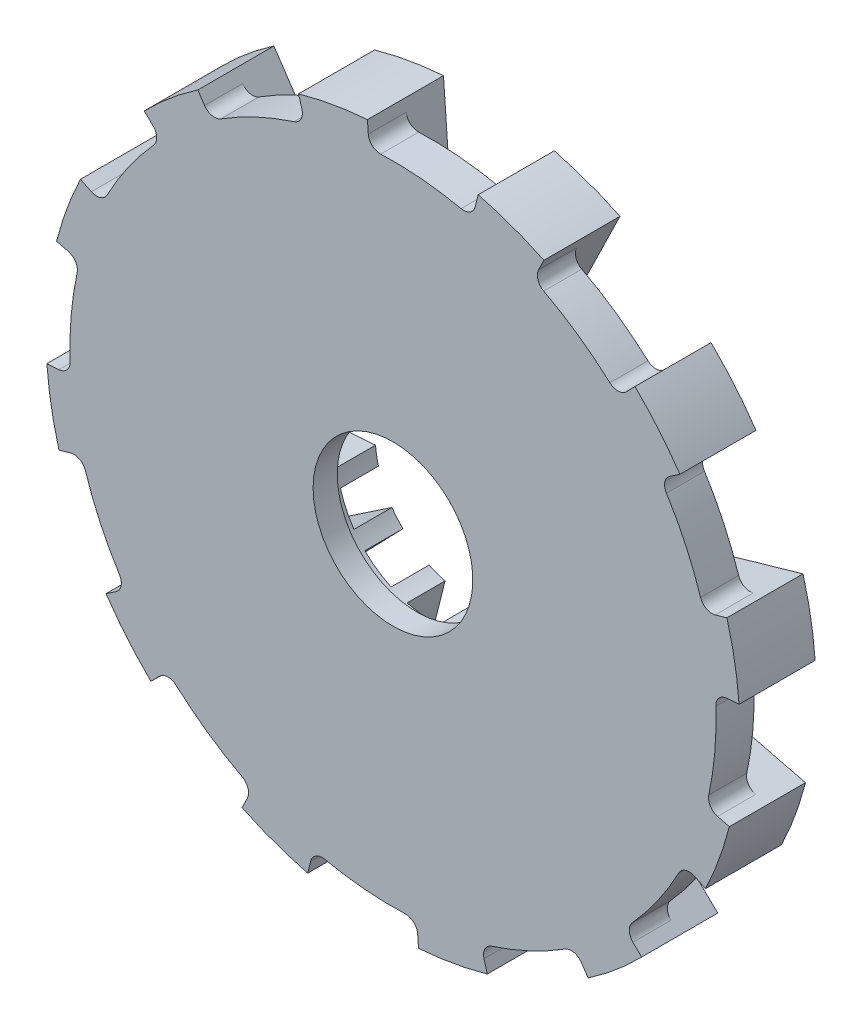
SolidWorks part; units mm, degrees
material "6061-T6 (SS)"
ref_plane "Front Plane" through (0, 0, 0) normal (1, 0, 0) x (0, 1, 0)
ref_plane "Top Plane" through (0, 0, 0) normal (0, 0, 1) x (0, 1, 0)
ref_plane "Right Plane" through (0, 0, 0) normal (0, 1, 0) x (-1, 0, 0)
ref_axis "Axis1" through (0, 0, 20.005) along (0, 0, -1)
sketch "Sketch1" plane through (0, 0, 0) normal (0, 0, 1) x (0, 1, 0)
  line L0 (0, 0) -> (0, 101.4736) construction
  line L1 (0, 0) -> (-35.1798, 75.4434) construction
  line L2 (-48.8686, 71.8573) -> (-10.3133, 14.6967)
  line L3 (-4.6291, 17.3473) -> (-23.6338, 83.6245)
  line L4 (-44.6805, 71.0131) -> (-25.6791, 79.8736) construction
  circle A0 centre (0, 0) radius 86.9
  arc A2 (-10.3133, 14.6967) -> (-4.6291, 17.3473) centre (-7.6811, 16.4721) ccw
  arc A3 (-46.2782, 73.5523) -> (-26.5973, 82.7296) centre (0, 0) cw
  arc A4 (-43.0829, 68.4739) -> (-24.7609, 77.0176) centre (0, 0) cw
  arc A7 (-46.2782, 73.5523) -> (-43.0829, 68.4739) centre (-44.6805, 71.0131) ccw
  arc A8 (-26.5973, 82.7296) -> (-24.7609, 77.0176) centre (-25.6791, 79.8736) cw
  point P4 (0, 0)
  point P11 (-6.6544, 77.2704)
  point P13 (-6.3393, 13.5946)
  point P16 (0, 0)
  point P19 (-48.8686, 71.8573)
  point P20 (0, 0)
  dimension "D1" = 173.8
  dimension "D2" = 86.9
  dimension "D5" = 15
  dimension "D6" = 3
  dimension "D7" = 16
  dimension "D3" = 3.175
  dimension "D4" = 34
sketch "Sketch4" plane through (0, 0, 0) normal (1, 0, 0) x (0, 1, 0)
  line L0 (-20, 19.05) -> (-86.9, 19.05)
  line L2 (-86.9, 19.05) -> (-86.9, 0)
  line L4 (-86.9, 0) -> (-23.5, 0)
  line L5 (-23.5, 0) -> (-23.5, 13)
  line L6 (-23.5, 13) -> (-20, 13)
  line L7 (-20, 13) -> (-20, 19.05)
  line L8 (0, 0) -> (0, 19.05) construction
  point P19 (-84.9, 16.0843)
  dimension "D1" = 47
  dimension "D2" = 40
  dimension "D3" = 13
  dimension "D4" = 173.8
  dimension "D5" = 19.05
revolve "Revolve1" add sketch "Sketch4" angle 360 about L8 region at (0, -54.6236, 9.637)
extrude "Cut-Extrude1" cut sketch "Sketch1<4>" against normal through all both and the other way through all contours A8 A3 A7 A4 | A7 A0 L2 | A0 A8 L3 region at (-71.6799, -47.9137, 0) region at (-75.7678, -35.3311, 0) region at (-82.779, -24.1117, 0)
sketch "Sketch1<4>" plane through (0, 0, 0) normal (0, 0, 1) x (0, 1, 0) same geometry as "Sketch1"
extrude "Cut-Extrude2" cut sketch "Sketch1" along normal blind 9.525 contours L3 A8 A4 A7 L2 A2 region at (-49.9878, -23.3097, 0)
pattern_circular "CirPattern2" count 12 over 360 about axis through (0, 0, 20.005) along (0, 0, -1) of "Cut-Extrude1", "Cut-Extrude2"
